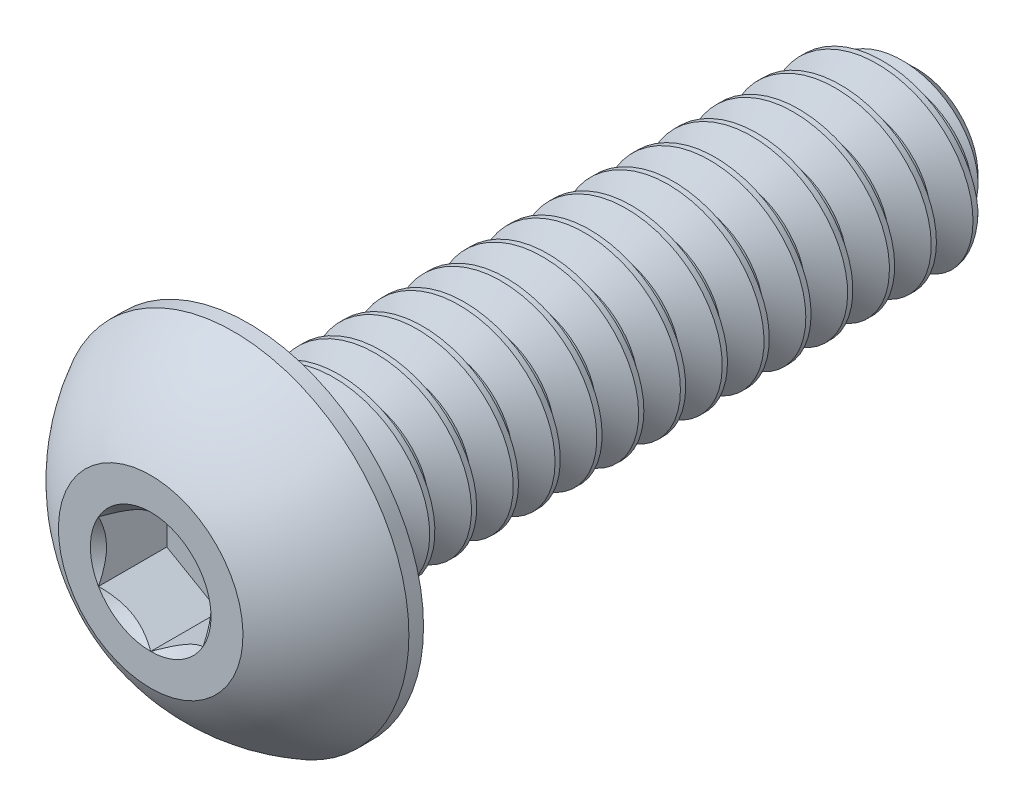
SolidWorks part; units mm, degrees
ref_plane "Front" through (0, 0, 0) normal (0, 0, 1) x (1, 0, 0)
ref_plane "Top" through (0, 0, 0) normal (0, 1, 0) x (1, 0, 0)
ref_plane "Right" through (0, 0, 0) normal (1, 0, 0) x (0, 0, -1)
sketch "Sketch1" plane through (0, 0, 0) normal (1, 0, 0) x (0, 0, -1)
  line L2 (1.8542, 1.7526) -> (14.5542, 1.7526)
  line L3 (14.5542, 1.7526) -> (14.5542, 0)
  line L4 (14.5542, 0) -> (1.8542, 0)
  line L6 (1.5761, 3.3274) -> (1.8542, 3.3274) construction
  line L7 (14.5542, 1.7526) -> (14.5542, -1.7526) construction
  line L8 (0, 0) -> (1.8542, 0) construction
  line L9 (1.8542, 3.3274) -> (1.8542, -3.3274) construction
  line L11 (1.8542, 1.7526) -> (1.8542, 0)
  line L13 (0, 0.9922) -> (0, -0.9922) construction
  line L14 (0, 0.9922) -> (0, 1.7526) construction
  arc A3 (0, 1.7526) -> (1.5761, 3.3274) centre (3.326, 0) cw construction
  dimension "D1" = 0.2781
revolve "Revolve1" add sketch "Sketch1" angle 360 mid plane about L4
sketch "Sketch3" plane through (0, 0, -14.5542) normal (0, 0, -1) x (-1, 0, 0)
  circle A0 centre (0, 0) radius 1.7526
curve "Helix/Spiral1" pitch 0.7937 height 13.4937 turns 17
sketch "Sketch2" plane through (0, 0, 0) normal (1, 0, 0) x (0, 0, -1)
  line L0 (14.5542, 1.7526) -> (15.2487, 1.7526)
  line L1 (15.2487, 1.7526) -> (14.9511, 1.237)
  line L2 (14.9511, 1.237) -> (14.8519, 1.237)
  line L3 (14.8519, 1.237) -> (14.5542, 1.7526)
  line L4 (14.703, 1.4948) -> (15.0999, 1.4948) construction
  dimension "D1" = 60
  dimension "D2" = 0.0992
  dimension "D3" = 0.3969
chamfer "Chamfer1" distance 0.5953 angle 45 1 edges at (0, 1.7526, -14.5542)
sweep "Cut-Sweep1" cut profiles "Sketch2" path "Helix/Spiral1" align with end faces yes
sketch "Sketch7" plane through (0, 0, 0) normal (1, 0, 0) x (0, 0, -1)
  line L6 (1.5761, 3.3274) -> (1.8542, 3.3274) construction
  line L8 (0, 0) -> (1.8542, 0) construction
  line L11 (1.8542, 3.3274) -> (1.8542, -3.3274) construction
  line L12 (1.5761, 3.3274) -> (1.8542, 3.3274)
  line L13 (0, 0) -> (1.8542, 0)
  line L14 (0, 0.9922) -> (0, -0.9922) construction
  line L15 (1.8542, 3.3274) -> (1.8542, 0)
  line L16 (0, 1.7526) -> (0, 0)
  arc A2 (1.5761, 3.3274) -> (0, 1.7526) centre (3.326, 0) ccw construction
  arc A3 (1.5761, 3.3274) -> (0, 1.7526) centre (3.326, 0) ccw
revolve "Revolve2" add sketch "Sketch7" angle 360 mid plane about L13
sketch "Sketch5" plane through (0, 0, 0) normal (0, 0, 1) x (1, 0, 0)
  line L1 (0.9922, -0.5728) -> (0.9922, 0.5728)
  line L2 (0.9922, 0.5728) -> (0, 1.1457)
  line L3 (0, 1.1457) -> (-0.9922, 0.5728)
  line L4 (-0.9922, 0.5728) -> (-0.9922, -0.5728)
  line L5 (-0.9922, -0.5728) -> (0, -1.1457)
  line L6 (0, -1.1457) -> (0.9922, -0.5728)
  circle A0 centre (0, 0) radius 0.9922 construction
extrude "Cut-Extrude2" cut sketch "Sketch5" against normal blind 1.2979
sketch "Sketch6" plane through (0, 0, 0) normal (0, 0, 1) x (1, 0, 0)
  circle A0 centre (0, 0) radius 1.1457
extrude "Cut-Extrude3" cut sketch "Sketch6" against normal blind 1.2979 draft 45
sketch "Sketch9" [suppressed] plane through (0, 0, -1.4986) normal (0, 0, 1) x (1, 0, 0)
  circle A2 centre (0, 0) radius 1.4224
extrude "Boss-Extrude2" [suppressed] add sketch "Sketch9" against normal offset from surface (12.7 mm away) 31.75
sketch "Sketch10" plane through (0, 0, 0) normal (1, 0, 0) x (0, 0, -1)
  line L0 (14.5542, 1.7526) -> (14.5542, -1.7526) construction
  point P0 (13.3636, -1.7526)
  dimension "D1" = 1.1906
equation "\"D3@Helix/Spiral1\" = \"Lg@Sketch1\" + \"D4@Helix/Spiral1\""
equation "\"D2@Sketch2\" = \"D4@Helix/Spiral1\" * .125"
equation "\"D3@Sketch2\" = \"D4@Helix/Spiral1\" * .5"
equation "\"D1@Chamfer1\" = \"D4@Helix/Spiral1\" * .75"
equation "\"D1@Cut-Extrude2\" = \"Head Ht@Sketch1\" * .7"
equation "\"D1@Sketch1\" = \"Head Ht@Sketch1\" * .15"
equation "\"D1@Sketch10\" = \"D4@Helix/Spiral1\" * 1.5"
equation "\"D1@Cut-Extrude3\" = \"D1@Cut-Extrude2\""
